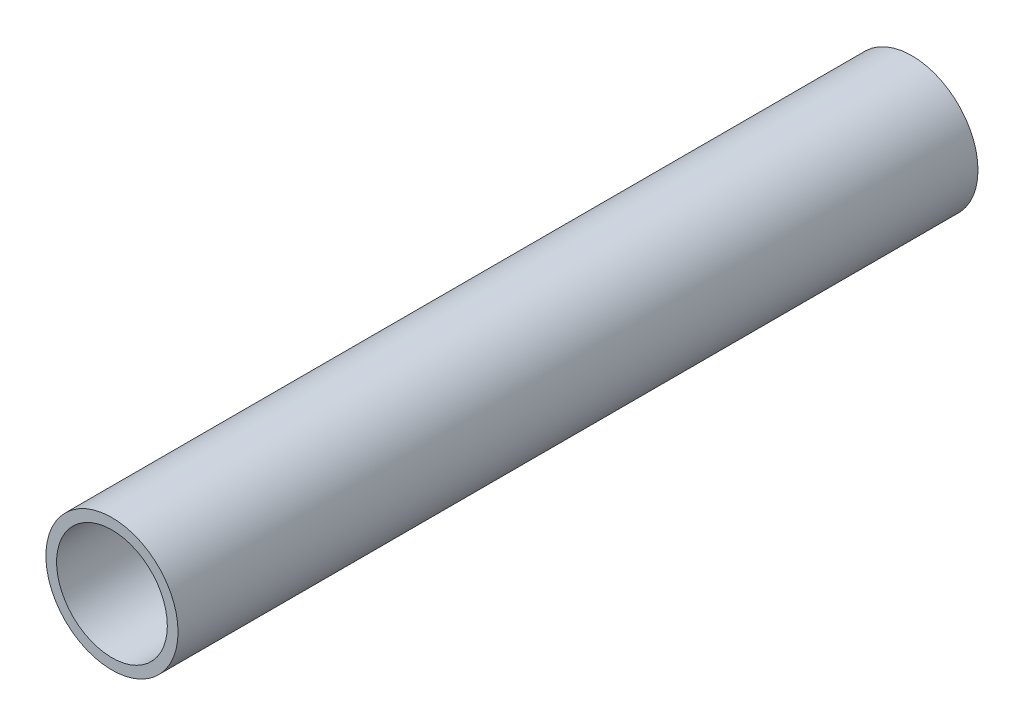
SolidWorks part; units mm, degrees
material "PVC Rigid"
ref_plane "Front Plane" through (0, 0, 0) normal (0, 0, 1) x (1, 0, 0)
ref_plane "Top Plane" through (0, 0, 0) normal (0, 1, 0) x (1, 0, 0)
ref_plane "Right Plane" through (0, 0, 0) normal (1, 0, 0) x (0, 0, -1)
sketch "Sketch1" plane through (0, 0, 0) normal (0, 0, 1) x (1, 0, 0)
  circle A0 centre (-325.6373, 52.475) radius 24.13
  circle A1 centre (-325.6373, 52.475) radius 20.2184
  dimension "D1" = 48.26
  dimension "D2" = 3.9116
extrude "Boss-Extrude1" add sketch "Sketch1" against normal blind 292.1
ref_plane "Plane1" through (0, 28.345, 0) normal (0, -1, 0) x (-1, 0, 0)
hole_wizard "1/4 (0.25) Diameter Hole1" positions "Sketch2" profile "Sketch3" hole size "1/4" standard "ANSI Inch" end condition up to next
sketch "Sketch2" plane through (0, 28.345, 0) normal (0, -1, 0) x (-1, 0, 0)
  circle A0 centre (325.6373, 50.8) radius 2.4574 construction
  circle A1 centre (325.6373, 241.3) radius 2.4574 construction
  point P0 (325.6373, 50.8)
  point P2 (325.6373, 241.3)
sketch "Sketch3" plane through (-325.6373, 28.345, -50.8) normal (1, 0, 0) x (0, 0, -1)
  line L0 (0, 0) -> (0, 3.9116)
  line L1 (0, 3.9116) -> (3.175, 3.9116)
  line L2 (3.175, 3.9116) -> (3.175, 0)
  line L5 (3.175, 0) -> (0, 0)
  line L11 (0, -6.35) -> (0, 107.95) construction
  dimension "Thru Hole Dia." = 6.35
  dimension "Thru Hole Depth" = 3.9116
